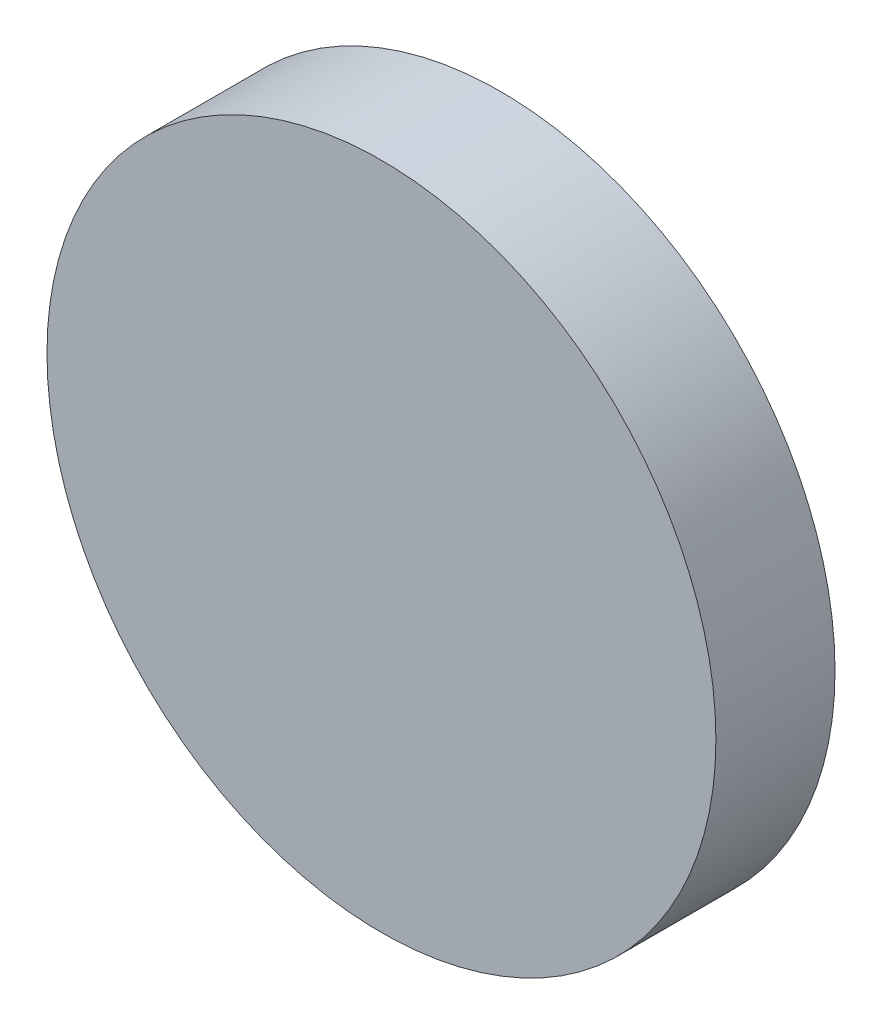
SolidWorks part; units mm, degrees
ref_plane "Front Plane" through (0, 0, 0) normal (0, 0, 1) x (1, 0, 0)
ref_plane "Top Plane" through (0, 0, 0) normal (0, 1, 0) x (1, 0, 0)
ref_plane "Right Plane" through (0, 0, 0) normal (1, 0, 0) x (0, 0, -1)
sketch "Sketch1" plane through (0, 0, 0) normal (0, 0, 1) x (1, 0, 0)
  circle A0 centre (0, 0) radius 46.355
  dimension "D1" = 92.71
extrude "Boss-Extrude1" add sketch "Sketch1" along normal blind 3.81
sketch "Sketch4" plane through (0, 0, 0) normal (0, 0, -1) x (-1, 0, 0)
  circle A0 centre (0, 0) radius 46.355
  circle A1 centre (0, 0) radius 44.45
  dimension "D1" = 88.9
  dimension "D2" = 92.71
extrude "Boss-Extrude2" add sketch "Sketch4" along normal blind 12.7
sketch "Sketch7" plane through (0, 0, 0) normal (0, 0, -1) x (-1, 0, 0)
  line L0 (-44.3842, -2.4176) -> (44.3842, -2.4176) construction
  line L1 (0, 44.45) -> (0, -43.7762) construction
  line L2 (-0.0792, -0.3493) -> (-0.0792, 44.1007) construction
  line L3 (-40.283, 5.5885) -> (40.1247, 5.5885) construction
  line L4 (-44.4782, 1.7785) -> (44.3199, 1.7785) construction
  line L5 (-40.283, 5.5885) -> (-44.4782, 1.7785) construction
  line L6 (40.1247, 5.5885) -> (44.3199, 1.7785) construction
  line L8 (-44.4546, -2.4176) -> (44.4454, -2.4176)
  line L9 (-44.4546, -2.4176) -> (-44.4546, -0.6396)
  line L10 (-44.4546, -0.6396) -> (44.4454, -0.6396)
  line L11 (44.4454, -2.4176) -> (44.4454, -0.6396)
  circle A0 centre (0, 0) radius 44.45 construction
  circle A1 centre (0, 0) radius 44.45 construction
  arc A2 (44.3199, 1.7785) -> (-44.4782, 1.7785) centre (-0.0792, -0.3493) ccw construction
  arc A3 (40.1247, 5.5885) -> (-40.283, 5.5885) centre (-0.0792, -0.3493) ccw construction
  dimension "D1" = 88.9
  dimension "D2" = 88.9
  dimension "D3" = 3.81
  dimension "D4" = 1.778
equation "\"D1@Boss-Extrude1\"=0.15"
